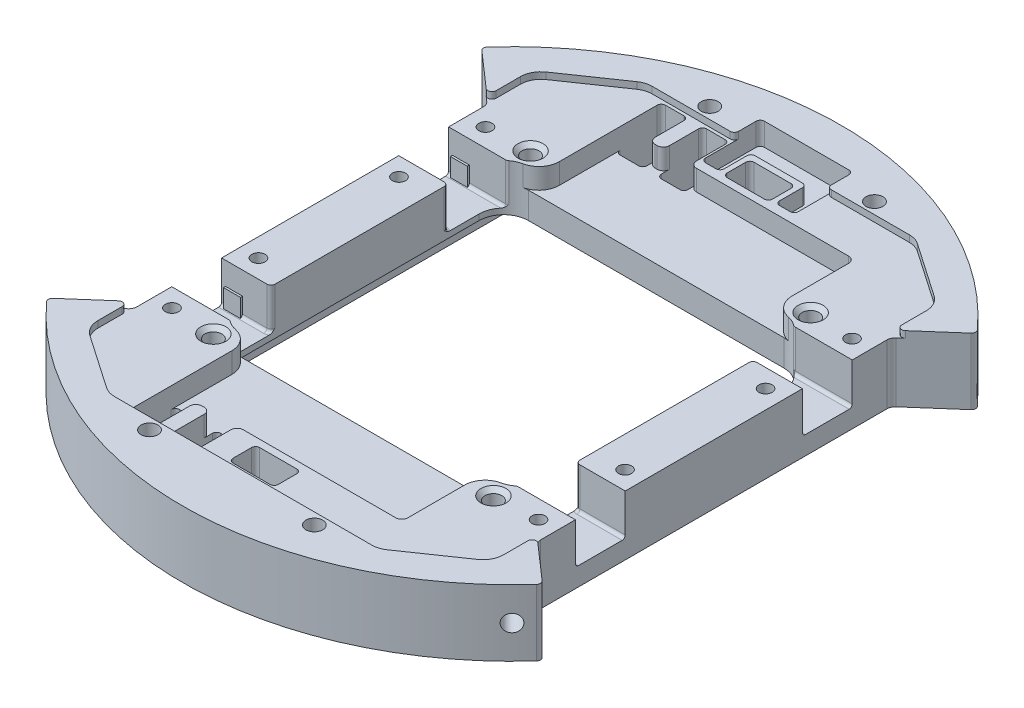
SolidWorks part; units mm, degrees
ref_plane "Спереди" through (0, 0, 0) normal (0, 0, 1) x (1, 0, 0)
ref_plane "Сверху" through (0, 0, 0) normal (0, 1, 0) x (1, 0, 0)
ref_plane "Справа" through (0, 0, 0) normal (1, 0, 0) x (0, 0, -1)
sketch "Эскиз1" plane through (0, 0, 0) normal (0, 1, 0) x (1, 0, 0)
  line L0 (0, 2.2921) -> (0, 50002.2921) construction
  line L1 (0, 0) -> (50000, 0) construction
  line L3 (-49, 42.0565) -> (-49, -42.0565)
  line L8 (-64.5, 27.5565) -> (-20, 27.5565) construction
  line L9 (-64.5, 42.0565) -> (-51, 42.0565) construction
  line L10 (-64.5, 42.0565) -> (-64.5, 13.0565) construction
  line L11 (-64.5, 13.0565) -> (-51, 13.0565) construction
  line L12 (-51, 42.0565) -> (-51, 13.0565) construction
  line L13 (-64.5, 42.0565) -> (-67.013, 43.6951) construction
  line L14 (-49.6815, 43.5603) -> (-60.1527, 52.7414)
  line L15 (-37, 29) -> (-37, -29)
  line L16 (-20, 33.5565) -> (-49, 33.5565) construction
  line L17 (-20, 33.5565) -> (-20, 21.5565) construction
  line L18 (-20, 21.5565) -> (-49, 21.5565) construction
  line L19 (-49, 33.5565) -> (-49, 21.5565) construction
  line L20 (-31, 35) -> (31, 35)
  line L21 (-49, 65) -> (-49, -65) construction
  line L22 (-49, 65) -> (49, 65) construction
  line L23 (-49, -65) -> (49, -65) construction
  line L24 (49, 65) -> (49, -65) construction
  line L25 (-31, -35) -> (31, -35)
  line L26 (37, 29) -> (37, -29)
  line L27 (-49.6815, -43.5603) -> (-60.1527, -52.7414)
  line L28 (49, 42.0565) -> (49, -42.0565)
  line L29 (49.6815, 43.5603) -> (60.1527, 52.7414)
  line L30 (49.6815, -43.5603) -> (60.1527, -52.7414)
  line L31 (49.25, 43.0248) -> (49.25, 53.9097)
  line L32 (49.25, 53.9097) -> (32.7758, 65.25)
  line L33 (32.7758, 65.25) -> (-32.7758, 65.25)
  line L34 (-49.25, 43.0248) -> (-49.25, 53.9097)
  line L35 (-49.25, 53.9097) -> (-32.7758, 65.25)
  line L36 (49.25, -43.0248) -> (49.25, -53.9097)
  line L37 (49.25, -53.9097) -> (32.7758, -65.25)
  line L38 (32.7758, -65.25) -> (-32.7758, -65.25)
  line L39 (-49.25, -53.9097) -> (-32.7758, -65.25)
  line L40 (-49.25, -43.0248) -> (-49.25, -53.9097)
  line L42 (-5.5, 56.75) -> (5.5, 56.75)
  line L43 (-5.5, 56.75) -> (-5.5, 63.25)
  line L44 (-5.5, 63.25) -> (5.5, 63.25)
  line L45 (5.5, 56.75) -> (5.5, 63.25)
  line L46 (-5.5, 56.75) -> (5.5, 63.25) construction
  line L47 (-5.5, 63.25) -> (5.5, 56.75) construction
  line L48 (-28.25, 53.5) -> (-21.75, 53.5)
  line L49 (-28.25, 53.5) -> (-28.25, 64.5)
  line L50 (-28.25, 64.5) -> (-21.75, 64.5)
  line L51 (-21.75, 53.5) -> (-21.75, 64.5)
  line L52 (-28.25, 53.5) -> (-21.75, 64.5) construction
  line L53 (-28.25, 64.5) -> (-21.75, 53.5) construction
  line L57 (-28.25, -64.5) -> (-21.75, -64.5)
  line L58 (-21.75, -53.5) -> (-21.75, -64.5)
  line L59 (-28.25, -53.5) -> (-21.75, -53.5)
  line L60 (-28.25, -53.5) -> (-28.25, -64.5)
  line L61 (-5.5, -63.25) -> (5.5, -63.25)
  line L62 (5.5, -56.75) -> (5.5, -63.25)
  line L63 (-5.5, -56.75) -> (5.5, -56.75)
  line L64 (-5.5, -56.75) -> (-5.5, -63.25)
  line L69 (0, 0) -> (41.0129, 59.5799) construction
  line L70 (-25, 60) -> (0, 60) construction
  line L71 (-11.75, 53.5) -> (-18.25, 53.5)
  line L72 (-11.75, 53.5) -> (-11.75, 64.5)
  line L73 (-11.75, 64.5) -> (-18.25, 64.5)
  line L74 (-18.25, 53.5) -> (-18.25, 64.5)
  line L75 (-11.75, 53.5) -> (-18.25, 64.5) construction
  line L76 (-11.75, 64.5) -> (-18.25, 53.5) construction
  line L77 (-30.0166, 59) -> (-6.2668, 59) construction
  line L78 (-11.75, -53.5) -> (-18.25, -53.5)
  line L79 (-11.75, -53.5) -> (-11.75, -64.5)
  line L80 (-11.75, -64.5) -> (-18.25, -64.5)
  line L81 (-18.25, -53.5) -> (-18.25, -64.5)
  circle A0 centre (0, 0) radius 80 construction
  arc A1 (-60.1527, 52.7414) -> (60.1527, 52.7414) centre (0, 0) cw
  arc A3 (-60.1527, -52.7414) -> (60.1527, -52.7414) centre (0, 0) ccw
  arc A4 (-49, 42.0565) -> (-49.6815, 43.5603) centre (-51, 42.0565) ccw
  arc A5 (-37, 29) -> (-31, 35) centre (-31, 29) cw
  arc A6 (37, 29) -> (31, 35) centre (31, 29) ccw
  arc A7 (-37, -29) -> (-31, -35) centre (-31, -29) ccw
  arc A8 (37, -29) -> (31, -35) centre (31, -29) cw
  circle A9 centre (-44.5, 38.0565) radius 4.5 construction
  circle A10 centre (-44.5, 38.0565) radius 1.6
  circle A11 centre (-44.5, 17.0565) radius 1.6
  circle A12 centre (-44.5, -17.0565) radius 1.6
  circle A13 centre (-44.5, -38.0565) radius 1.6
  circle A14 centre (44.5, -38.0565) radius 1.6
  circle A15 centre (44.5, -17.0565) radius 1.6
  circle A16 centre (44.5, 17.0565) radius 1.6
  circle A17 centre (44.5, 38.0565) radius 1.6
  arc A18 (-49, -42.0565) -> (-49.6815, -43.5603) centre (-51, -42.0565) cw
  arc A19 (49, 42.0565) -> (49.6815, 43.5603) centre (51, 42.0565) cw
  arc A20 (49, -42.0565) -> (49.6815, -43.5603) centre (51, -42.0565) ccw
  point P0 (-15, 59)
  point P27 (-25, 59)
  point P28 (-20, 27.5565)
  point P32 (0, 60)
  point P77 (0, 60)
  point P87 (-25, 59)
  point P108 (41.0129, 59.5799)
  dimension "D1" = 160
  dimension "D12" = 6
  dimension "D17" = 9
  dimension "D18" = 3.2
  dimension "D2" = 29
  dimension "D3" = 13.5
  dimension "D4" = 2
  dimension "D5" = 3
  dimension "D6" = 55.113
  dimension "D7" = 12
  dimension "D8" = 29
  dimension "D9" = 12
  dimension "D10" = 59
  dimension "D11" = 50
  dimension "D13" = 1
  dimension "D14" = 98
  dimension "D15" = 130
  dimension "D16" = 20
  dimension "D19" = 30
  dimension "D20" = 0.25
  dimension "D21" = 0.25
  dimension "D22" = 70
  dimension "D23" = 11
  dimension "D24" = 6.5
  dimension "D25" = 6
extrude "Бобышка-Вытянуть1" add sketch "Эскиз1" along normal blind 14.5 contours L31 A19 L29 A1 L14 A4 L34 L35 L33 L32 | A20 L28 A19 L31 L32 L33 L35 L34 A4 L3 A18 L40 L39 L38 L37 L36 A15 A14 A11 A10 L26 A8 L25 A7 L15 A5 L20 A6 A12 A13 A16 A17 | A20 L36 L37 L38 L39 L40 A18 L27 A3 L30 region at (-47.4804, 0, -42.9653) region at (0, 0, -66.8376) region at (0, 0, 66.8376)
sketch "Эскиз2" plane through (0, 14.5, 0) normal (0, 1, 0) x (1, 0, 0)
  line L0 (0, 0) -> (50000, 0) construction
  line L1 (0, 0) -> (0, 50000) construction
  line L2 (-70.7859, 27.5565) -> (-8.6839, 27.5565) construction
  line L3 (-64.5, 27.5565) -> (-20, 27.5565) construction
  line L4 (-49, 21.5065) -> (-49, 33.6065)
  line L5 (-37, 33.6065) -> (37, 33.6065)
  line L6 (-49, 33.6065) -> (-37, 33.6065)
  line L7 (37, 21.5065) -> (-37, 21.5065)
  line L8 (-49, 21.5065) -> (-37, 21.5065)
  line L10 (-43.95, 33.6065) -> (-43.95, 33.1065)
  line L11 (-43.95, 33.1065) -> (-48.05, 33.1065)
  line L12 (-48.05, 33.1065) -> (-48.05, 33.6065)
  line L13 (-49, -21.5065) -> (-37, -21.5065)
  line L14 (-49, -21.5065) -> (-49, -33.6065)
  line L15 (-49, -33.6065) -> (-37, -33.6065)
  line L17 (49, -21.5065) -> (49, -33.6065)
  line L18 (49, -33.6065) -> (37, -33.6065)
  line L20 (49, 21.5065) -> (37, 21.5065)
  line L21 (49, 21.5065) -> (49, 33.6065)
  line L22 (49, 33.6065) -> (37, 33.6065)
  line L24 (49, -21.5065) -> (37, -21.5065)
  line L25 (-48.05, -21.5065) -> (-48.05, -22.0065)
  line L26 (-48.05, -22.0065) -> (-43.95, -22.0065)
  line L27 (-43.95, -22.0065) -> (-43.95, -21.5065)
  line L28 (43.95, 21.5065) -> (43.95, 22.0065)
  line L29 (43.95, 22.0065) -> (48.05, 22.0065)
  line L30 (48.05, 22.0065) -> (48.05, 21.5065)
  line L31 (43.95, -33.6065) -> (43.95, -33.1065)
  line L32 (43.95, -33.1065) -> (48.05, -33.1065)
  line L33 (48.05, -33.1065) -> (48.05, -33.6065)
  line L34 (-49, 42.0565) -> (-49, -42.0565) construction
  line L35 (-37, 29) -> (-37, -29) construction
  line L36 (-37, -21.5065) -> (37, -21.5065)
  line L37 (37, -33.6065) -> (-37, -33.6065)
  dimension "D1" = 0.95
  dimension "D2" = 4.1
  dimension "D3" = 0.5
  dimension "D4" = 12.1
  dimension "D5" = 0.95
extrude "Вырез-Вытянуть1" cut sketch "Эскиз2" against normal blind 10 contours L11 L12 L6 L8 L10 | L12 L11 L10 L6 | L27 L26 L25 L13 L15 | L26 L27 L13 L25 | L29 L30 L20 L22 L28 | L30 L29 L28 L20 | L32 L33 L18 L24 L31 | L33 L32 L31 L18 region at (0, 14.5, -27.5565) region at (-46, 14.5, -33.3565) region at (46, 14.5, -21.7565) region at (0, 14.5, 27.5565) region at (-46, 14.5, 21.7565) region at (46, 14.5, 33.3565)
fillet "Скругление8" radius 1 8 edges at (-37, 9.5, 21.5065) (-34.8445, 9.5, 33.6065) (34.8445, 9.5, 33.6065) (37, 9.5, 21.5065) (37, 9.5, -21.5065) (34.8445, 9.5, -33.6065) (-37, 9.5, -21.5065) (-34.8445, 9.5, -33.6065)
fillet "Скругление5" radius 1 24 edges at (5.5, 7.25, -56.75) (-5.5, 7.25, -56.75) (-5.5, 7.25, -63.25) (5.5, 7.25, -63.25) (-21.75, 7.25, -53.5) (-28.25, 7.25, -53.5) (-28.25, 7.25, -64.5) (-21.75, 7.25, -64.5) (-18.25, 7.25, 64.5) (-11.75, 7.25, 64.5) (-18.25, 7.25, 53.5) (-28.25, 7.25, 53.5) (-21.75, 7.25, 53.5) (-21.75, 7.25, 64.5) (-28.25, 7.25, 64.5) (-5.5, 7.25, 56.75) (5.5, 7.25, 56.75) (5.5, 7.25, 63.25) (-5.5, 7.25, 63.25) (-11.75, 7.25, 53.5) (-18.25, 7.25, -64.5) (-18.25, 7.25, -53.5) (-11.75, 7.25, -53.5) (-11.75, 7.25, -64.5)
fillet "Скругление4" radius 0.75 16 edges at (-43.5, 4.5, 21.5065) (42.0957, 4.5, 33.6065) (43.5, 4.5, -21.5065) (42.0957, 4.5, -33.6065) (43.5, 4.5, 21.5065) (-42.0957, 4.5, 33.6065) (-43.5, 4.5, -21.5065) (-42.0957, 4.5, -33.6065) (37.2929, 4.5, 21.2136) (34.8758, 4.5, 33.6576) (37.2929, 4.5, -21.2136) (34.8758, 4.5, -33.6576) (-37.2929, 4.5, 21.2136) (-34.8758, 4.5, 33.6576) (-37.2929, 4.5, -21.2136) (-34.8758, 4.5, -33.6576)
extrude "Бобышка-Вытянуть2" add sketch "Эскиз2<3>" along normal blind 4.5 from surface contours L12 L11 L10 L6 | L26 L27 L13 L25 | L33 L32 L31 L18 | L30 L29 L28 L20 region at (-46, 14.5, -33.3565) region at (46, 14.5, -21.7565) region at (-46, 14.5, 21.7565) region at (46, 14.5, 33.3565) starting at face at (-40.9854, 4.5, 26.8948)
sketch "Эскиз2<3>" plane through (0, 14.5, 0) normal (0, 1, 0) x (1, 0, 0) same geometry as "Эскиз2"
extrude "Бобышка-Вытянуть3" add sketch "Эскиз1<3>" along normal blind 1.6 from surface contours A20 L36 L37 L38 L39 L40 A18 L27 A3 L30 | L31 A19 L29 A1 L14 A4 L34 L35 L33 L32 region at (0, 0, -66.8376) region at (0, 0, 66.8376) starting at face at (44.5, 14.5, -15.4565)
sketch "Эскиз1<3>" plane through (0, 0, 0) normal (0, 1, 0) x (1, 0, 0) same geometry as "Эскиз1"
fillet "Скругление1" radius 5 8 edges at (-49.25, 15.3, 53.9097) (-32.7758, 15.3, 65.25) (32.7758, 15.3, 65.25) (49.25, 15.3, 53.9097) (49.25, 15.3, -53.9097) (32.7758, 15.3, -65.25) (-49.25, 15.3, -53.9097) (-32.7758, 15.3, -65.25)
fillet "Скругление2" radius 1 4 edges at (49.25, 15.3, 43.0248) (-49.25, 15.3, 43.0248) (49.25, 15.3, -43.0248) (-49.25, 15.3, -43.0248)
fillet "Скругление3" radius 1 4 edges at (-60.1527, 8.05, 52.7414) (-60.1527, 8.05, -52.7414) (60.1527, 8.05, -52.7414) (60.1527, 8.05, 52.7414)
sketch "Эскиз5" plane through (0, 0, 0) normal (0, -1, 0) x (1, 0, 0)
  line L0 (0, 0) -> (0, 50000) construction
  line L1 (0, 0) -> (50000, 0) construction
  line L2 (-38.5, 38.5) -> (-38.5, -38.5)
  line L4 (-34, 43) -> (34, 43)
  line L5 (-37, -29) -> (-37, 29) construction
  line L6 (-31, 35) -> (31, 35) construction
  line L7 (38.5, 38.5) -> (38.5, -38.5)
  line L8 (-34, -43) -> (34, -43)
  arc A0 (-38.5, 38.5) -> (-34, 43) centre (-34, 38.5) cw
  circle A1 centre (-34, 38.5) radius 1.6
  arc A2 (38.5, 38.5) -> (34, 43) centre (34, 38.5) ccw
  circle A3 centre (34, 38.5) radius 1.6
  circle A4 centre (34, -38.5) radius 1.6
  arc A5 (38.5, -38.5) -> (34, -43) centre (34, -38.5) cw
  circle A6 centre (-34, -38.5) radius 1.6
  arc A7 (-38.5, -38.5) -> (-34, -43) centre (-34, -38.5) ccw
  dimension "D1" = 4.5
  dimension "D3" = 3.2
  dimension "D2" = 1.5
  dimension "D4" = 8
extrude "Вырез-Вытянуть2" cut sketch "Эскиз5" against normal blind 3.1 contours L4 A2 L7 A5 L8 A7 L2 A0
extrude "Вырез-Вытянуть3" cut sketch "Эскиз5<3>" against normal through all both and the other way through all contours A1 | A3 | A6 | A4
sketch "Эскиз5<3>" plane through (0, 0, 0) normal (0, -1, 0) x (1, 0, 0) same geometry as "Эскиз5"
sketch "Эскиз6" plane through (0, 14.5, 0) normal (0, -1, 0) x (1, 0, 0)
  line L0 (0, 0) -> (0, 50000) construction
  line L1 (0, 0) -> (50000, 0) construction
  circle A0 centre (-34, 38.5) radius 2.05
  circle A1 centre (34, 38.5) radius 2.05
  circle A2 centre (34, -38.5) radius 2.05
  circle A3 centre (-34, -38.5) radius 2.05
  dimension "D1" = 4.1
extrude "Вырез-Вытянуть4" cut sketch "Эскиз6" along normal blind 6
chamfer "Фаска1" distance 1 angle 45 4 edges at (34, 14.5, -40.55) (-34, 14.5, -36.45) (-34, 14.5, 36.45) (34, 14.5, 40.55)
sketch "Эскиз7" plane through (0, 0, 0) normal (0, -1, 0) x (1, 0, 0)
  line L0 (0, 0) -> (0, 50000) construction
  line L1 (0, 0) -> (50000, 0) construction
  circle A0 centre (-44.5, 38.0565) radius 2.05
  circle A1 centre (-44.5, 17.0565) radius 2.05
  circle A2 centre (44.5, 17.0565) radius 2.05
  circle A3 centre (44.5, 38.0565) radius 2.05
  circle A4 centre (44.5, -38.0565) radius 2.05
  circle A5 centre (44.5, -17.0565) radius 2.05
  circle A6 centre (-44.5, -17.0565) radius 2.05
  circle A7 centre (-44.5, -38.0565) radius 2.05
  dimension "D1" = 4.1
extrude "Вырез-Вытянуть5" cut sketch "Эскиз7" against normal blind 6
sketch "Эскиз8" plane through (0, 14.5, 0) normal (0, 1, 0) x (1, 0, 0)
  line L0 (0, 0) -> (50000, 0) construction
  line L1 (0, 0) -> (0, 50000) construction
  line L3 (-28.25, -55) -> (-28.25, 55)
  line L4 (-28.25, 55) -> (28.25, 55)
  line L5 (-27.25, 53.5) -> (-22.75, 53.5) construction
  line L6 (-28.25, 54.5) -> (-28.25, 63.5) construction
  line L10 (28.25, -55) -> (28.25, 55)
  line L13 (-28.25, -55) -> (28.25, -55)
  point P5 (28.25, -56.8539)
  dimension "D3" = 1.5
extrude "Вырез-Вытянуть6" cut sketch "Эскиз8" against normal blind 5
fillet "Скругление6" radius 5 4 edges at (-28.25, 12, -35) (-28.25, 12, 35) (28.25, 12, 35) (28.25, 12, -35)
fillet "Скругление7" radius 1.5 8 edges at (-21.75, 12, 55) (-21.75, 12, -55) (-11.75, 12, 55) (-18.25, 12, 55) (-18.25, 12, -55) (-11.75, 12, -55) (28.25, 12, -55) (28.25, 12, 55)
sketch "Эскиз9" plane through (0, 16.1, 0) normal (0, 1, 0) x (1, 0, 0)
  line L0 (0, 0.9998) -> (0, 50000.9998) construction
  line L1 (11.27, 71.54) -> (-11.27, 71.54)
  line L6 (-11.27, 71.54) -> (-11.27, 57.25)
  line L7 (-11.27, 57.25) -> (-6.73, 57.25)
  line L8 (-6.73, 57.25) -> (-6.73, 64.75)
  line L9 (-6.73, 64.75) -> (6.73, 64.75)
  line L10 (6.73, 57.25) -> (6.73, 64.75)
  line L11 (11.27, 57.25) -> (6.73, 57.25)
  line L12 (11.27, 71.54) -> (11.27, 57.25)
  line L13 (-8.84, 70.54) -> (-9.16, 70.54) construction
  line L14 (-10.27, 67.54) -> (-10.27, 65) construction
  line L15 (-7.73, 67.54) -> (-7.73, 65) construction
  line L16 (-31.2213, 65.25) -> (31.2213, 65.25) construction
  line L17 (0.7482, 0) -> (50000.7482, 0) construction
  line L18 (-4.5, 63.25) -> (4.5, 63.25) construction
  circle A0 centre (-20, 68) radius 1.6
  circle A2 centre (20, 68) radius 1.6
  circle A3 centre (-20, 68) radius 2.05
  circle A4 centre (20, 68) radius 2.05
  circle A5 centre (-20, -68) radius 2.05
  circle A6 centre (-20, -68) radius 1.6
  circle A7 centre (20, -68) radius 1.6
  circle A8 centre (20, -68) radius 2.05
  dimension "D7" = 3.2
  dimension "D8" = 4.1
  dimension "D1" = 1
  dimension "D2" = 1
  dimension "D3" = 1
  dimension "D4" = 8
  dimension "D5" = 40
  dimension "D6" = 68
  dimension "D9" = 1.5
extrude "Вырез-Вытянуть7" cut sketch "Эскиз9" against normal blind 5.5 contours L1 L6 L7 L8 L9 L10 L11 L12
fillet "Скругление9" radius 1 10 edges at (11.27, 12.55, -57.25) (6.73, 12.55, -57.25) (11.27, 13.35, -71.54) (6.73, 12.55, -64.75) (-6.73, 12.55, -64.75) (-6.73, 12.55, -57.25) (-11.27, 12.55, -57.25) (-11.27, 13.35, -71.54) (11.27, 15.3, -65.25) (-11.27, 15.3, -65.25)
extrude "Вырез-Вытянуть8" cut sketch "Эскиз9<3>" against normal blind 12 contours A0 | A2 | A6 | A7
sketch "Эскиз9<3>" plane through (0, 16.1, 0) normal (0, 1, 0) x (1, 0, 0) same geometry as "Эскиз9"
extrude "Вырез-Вытянуть9" cut sketch "Эскиз9<4>" against normal blind 6 contours A3 | A4 | A5 | A8
sketch "Эскиз9<4>" plane through (0, 16.1, 0) normal (0, 1, 0) x (1, 0, 0) same geometry as "Эскиз9"
ref_plane "Плоскость1" through (-56.5685, 0, -56.5685) normal (-0.7071, 0, -0.7071) x (0, -1, 0)
sketch "Эскиз10" plane through (-56.5685, 0, -56.5685) normal (-0.7071, 0, -0.7071) x (0, -1, 0)
  line L0 (0, 0) -> (-16.1, 0) construction
  line L2 (-16.1, 4.2297) -> (-16.1, -80) construction
  circle A0 centre (-8.05, 0) radius 2.05
  circle A1 centre (-8.05, 0) radius 1.6
  dimension "D1" = 4.1
  dimension "D2" = 3.2
extrude "Вырез-Вытянуть10" cut sketch "Эскиз10" against normal blind 15 contours A1
extrude "Вырез-Вытянуть11" cut sketch "Эскиз10<3>" against normal blind 6 contours A0
sketch "Эскиз10<3>" plane through (-56.5685, 0, -56.5685) normal (-0.7071, 0, -0.7071) x (0, -1, 0) same geometry as "Эскиз10"
pattern_circular "Круговой массив1" count 4 over 360 about axis through (0, 14.5, 0) along (0, -1, 0) of "Вырез-Вытянуть10", "Вырез-Вытянуть11"
sketch "Эскиз11" plane through (0, 0, 0) normal (0, -1, 0) x (1, 0, 0)
  line L0 (49.6815, -43.5603) -> (59.396, -52.078) construction
  line L2 (49.6815, 43.5603) -> (59.396, 52.078) construction
  arc A0 (54.8893, -48.1265) -> (25.4765, -68.4102) centre (0, 0) cw construction
  arc A2 (-59.4802, -53.4986) -> (59.4802, -53.4986) centre (0, 0) ccw construction
  arc A3 (37.9085, 62.3854) -> (54.8893, 48.1265) centre (0, 0) cw construction
  text T0 "<b>Design by ilust</b>" font "GOST type A_SW" height 4
  text T1 "<b>Банка</b>" font "GOST type A_SW" height 4
  point P6 (51.3593, 51.877)
  point P7 (23.2967, 69.1828)
  point P8 (54.5387, 47.8191)
  point P9 (54.8893, 48.1265)
  point P16 (0, 0)
  point P17 (33.7092, 64.751)
  point P20 (37.9085, 62.3854)
  dimension "D1" = 7
extrude "Вырез-Вытянуть12" cut sketch "Эскиз11" against normal blind 0.5
equation "\"D5@Эскиз2\"=\"D1@Эскиз2\""
